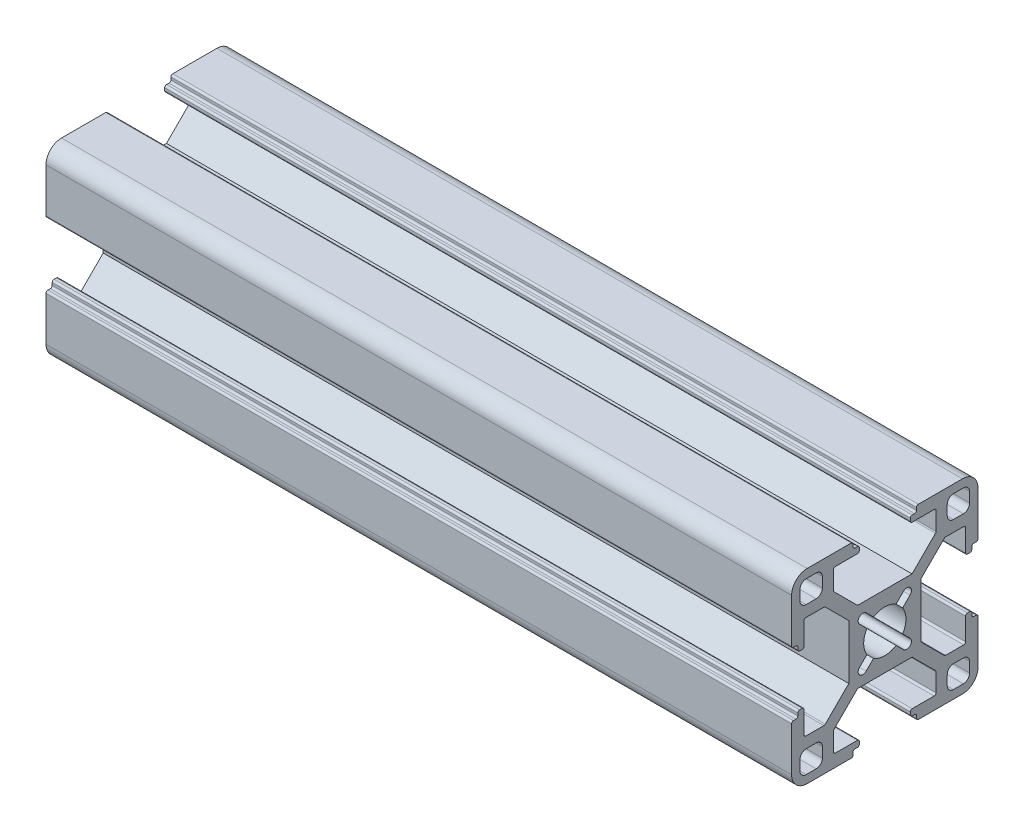
SolidWorks part; units mm, degrees
material "2.0572 (CuZn40Mn2Fe1)"
ref_plane "Front Plane" through (0, 0, 0) normal (0, 0, 1) x (1, 0, 0)
ref_plane "Top Plane" through (0, 0, 0) normal (0, 1, 0) x (1, 0, 0)
ref_plane "Right Plane" through (0, 0, 0) normal (1, 0, 0) x (0, 0, -1)
ref_axis "Axis_X" through (-58.3, 0, 0) along (1, 0, 0)
ref_axis "Axis_Y" through (0, 38.5, 0) along (0, -1, 0)
ref_axis "Axis_Z" through (0, 0, -4.5) along (0, 0, 1)
sketch "Sketch2" plane through (0, 0, 0) normal (1, 0, 0) x (0, 0, -1)
  line L1 (-15, 15) -> (15, 15)
  line L2 (-15, 15) -> (-15, -15)
  line L3 (-15, -15) -> (15, -15)
  line L4 (15, 15) -> (15, -15)
  line L5 (-15, 15) -> (15, -15) construction
  line L6 (-15, -15) -> (15, 15) construction
  point P0 (0, 0)
  dimension "D1" = 30
  dimension "D2" = 30
extrude "Boss-Extrude1" add sketch "Sketch2" along normal blind 120
sketch "Sketch5" plane through (120, 0, 0) normal (1, 0, 0) x (0, 0, -1)
  circle A0 centre (0, 0) radius 3.4
  dimension "D1" = 6.8
extrude "Cut-Extrude2" cut sketch "Sketch5" against normal through all
sketch "Sketch4" plane through (120, 0, 0) normal (1, 0, 0) x (0, 0, -1)
  line L0 (-4.3858, -5.8) -> (4.3858, -5.8)
  line L1 (4.3858, -5.8) -> (8.1621, -9.5763)
  line L2 (8.25, -9.7885) -> (8.25, -13)
  line L3 (8.25, -13) -> (4.1, -13)
  line L4 (4.1, -13) -> (4.1, -14)
  line L5 (4.1, -14) -> (5.1, -14)
  line L6 (5.1, -14) -> (5.1, -15)
  line L7 (-15, -15) -> (15, -15) construction
  line L8 (5.1, -15) -> (-5.1, -15)
  line L9 (-5.1, -15) -> (-5.1, -14)
  line L10 (-5.1, -14) -> (-4.1, -14)
  line L11 (-4.1, -14) -> (-4.1, -13)
  line L12 (-4.1, -13) -> (-8.25, -13)
  line L13 (-8.25, -13) -> (-8.25, -9.7885)
  line L14 (-8.1621, -9.5763) -> (-4.3858, -5.8)
  line L16 (-4.1, -13) -> (4.1, -13) construction
  line L17 (0, -14) -> (0, -15) construction
  line L18 (-4.1, -14) -> (4.1, -14) construction
  line L19 (0, -5.8) -> (0, -13) construction
  line L20 (0, -13) -> (0, -14) construction
  line L21 (15, -15) -> (15, 15) construction
  line L22 (11.05, -10.05) -> (12.65, -10.05)
  line L23 (10.05, -11.05) -> (10.05, -12.65)
  line L24 (11.05, -13.65) -> (12.65, -13.65)
  line L25 (13.65, -11.05) -> (13.65, -12.65)
  line L26 (10.05, -10.05) -> (13.65, -13.65) construction
  line L27 (10.05, -13.65) -> (13.65, -10.05) construction
  line L28 (0, 0) -> (3.5355, -3.5355) construction
  line L29 (15, -15) -> (15, 15) construction
  line L30 (4.0659, -3.0052) -> (2.8753, -1.8146)
  line L31 (3.0052, -4.0659) -> (1.8146, -2.8753)
  arc A0 (12.65, -13.65) -> (13.65, -12.65) centre (12.65, -12.65) ccw
  arc A1 (11.05, -13.65) -> (10.05, -12.65) centre (11.05, -12.65) cw
  arc A2 (10.05, -11.05) -> (11.05, -10.05) centre (11.05, -11.05) cw
  arc A3 (12.65, -10.05) -> (13.65, -11.05) centre (12.65, -11.05) cw
  arc A4 (3.0052, -4.0659) -> (4.0659, -3.0052) centre (3.5355, -3.5355) ccw
  circle A5 centre (0, 0) radius 3.4 construction
  arc A6 (1.8146, -2.8753) -> (2.8753, -1.8146) centre (0, 0) ccw
  arc A7 (-8.25, -9.7885) -> (-8.1621, -9.5763) centre (-7.95, -9.7885) cw
  arc A8 (8.25, -9.7885) -> (8.1621, -9.5763) centre (7.95, -9.7885) ccw
  point P18 (11.85, -11.85)
  point P47 (-8.25, -9.6642)
  point P55 (8.25, -9.6642)
  dimension "D11" = 1
  dimension "D14" = 1.5
  dimension "D2" = 0.3
  dimension "D1" = 9.2
  dimension "D3" = 1
  dimension "D4" = 8.2
  dimension "D5" = 10.2
  dimension "D6" = 16.5
  dimension "D7" = 2
  dimension "D8" = 1.35
  dimension "D9" = 1.35
  dimension "D10" = 3.6
  dimension "D12" = 45
  dimension "D13" = 5
  dimension "D15" = 5.4237
extrude "Cut-Extrude1" cut sketch "Sketch4" against normal through all
fillet "Fillet1" radius 2.5 1 edges at (60, -15, -15)
fillet "Fillet2" radius 0.3 10 edges at (60, -14, -5.1) (60, -15, -5.1) (60, -14, -4.1) (60, -13, -4.1) (60, -13, -8.25) (60, -13, 8.25) (60, -13, 4.1) (60, -14, 4.1) (60, -14, 5.1) (60, -15, 5.1)
pattern_circular "CirPattern1" count 4 over 360 about axis through (0, 0, 0) along (1, 0, 0) of "Cut-Extrude1", "Fillet1", "Fillet2"
equation "\"Factor\"= 1.082532"
